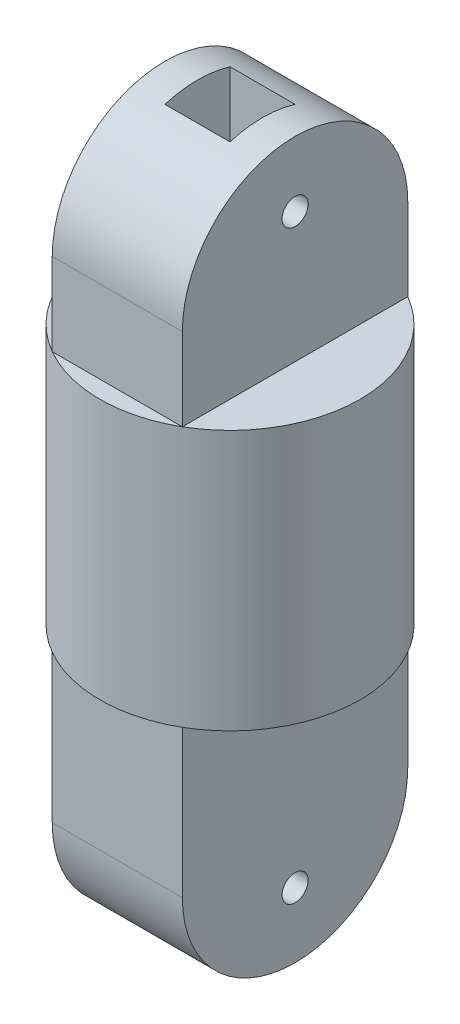
SolidWorks part; units mm, degrees
ref_plane "Front Plane" through (0, 0, 0) normal (0, 0, 1) x (1, 0, 0)
ref_plane "Top Plane" through (0, 0, 0) normal (0, 1, 0) x (1, 0, 0)
ref_plane "Right Plane" through (0, 0, 0) normal (1, 0, 0) x (0, 0, -1)
sketch "Sketch1" plane through (0, 0, 0) normal (0, 1, 0) x (1, 0, 0)
  circle A0 centre (0, 0) radius 5
  dimension "D1" = 10
extrude "Boss-Extrude1" add sketch "Sketch1" along normal blind 5 and the other way blind 5
sketch "Sketch2" plane through (0, -5, 0) normal (0, -1, 0) x (-1, 0, 0)
  line L0 (2.5, -4.3301) -> (2.5, 4.3301)
  line L1 (-2.5, -4.3301) -> (-2.5, 4.3301)
  line L2 (2.5, -4.3301) -> (-2.5, -4.3301)
  line L3 (2.5, 4.3301) -> (-2.5, 4.3301)
  circle A0 centre (0, 0) radius 5 construction
  point P4 (2.5, 0)
  dimension "D1" = 2.5
  dimension "D2" = 2.5
extrude "Boss-Extrude2" add sketch "Sketch2" along normal blind 10
sketch "Sketch3" plane through (-2.5, 0, 0) normal (-1, 0, 0) x (0, 0, 1)
  line L0 (4.3301, -15) -> (4.3301, -5) construction
  line L1 (4.3301, -15) -> (-4.3301, -15) construction
  line L2 (-4.3301, -15) -> (-4.3301, -5) construction
  line L3 (4.3301, -10.6699) -> (5.8429, -10.6699)
  line L4 (5.8429, -10.6699) -> (5.8429, -18.9142)
  line L5 (5.8429, -18.9142) -> (-6.8562, -18.9142)
  line L6 (-6.8562, -18.9142) -> (-6.8562, -10.6699)
  line L7 (-6.8562, -10.6699) -> (-4.3301, -10.6699)
  arc A0 (0, -15) -> (4.3301, -10.6699) centre (0, -10.6699) ccw
  arc A1 (0, -15) -> (-4.3301, -10.6699) centre (0, -10.6699) cw
  point P0 (0, -10.6699)
  point P5 (0, -15)
  dimension "D1" = 4.3301
  dimension "D2" = 4.3301
extrude "Cut-Extrude1" cut sketch "Sketch3" against normal blind 10
sketch "Sketch4" plane through (-2.5, 0, 0) normal (-1, 0, 0) x (0, 0, 1)
  arc A0 (-4.3301, -10.6699) -> (4.3301, -10.6699) centre (0, -10.6699) ccw construction
  point P0 (0, -12.5)
  point P4 (0, -15)
  dimension "D1" = 2.5
hole_wizard "#95 (0.03937008) Diameter Hole1" positions "Sketch5" profile "Sketch6" hole size "#95" standard "ANSI Inch" end condition through all
sketch "Sketch5" plane through (-2.5, 0, 0) normal (-1, 0, 0) x (0, 0, 1)
  point P0 (0, -12.5)
sketch "Sketch6" plane through (-2.5, -12.5, 0) normal (0, 1, 0) x (0, 0, 1)
  line L0 (0, 0) -> (0, 7.5)
  line L1 (0, 7.5) -> (0.5, 7.5)
  line L2 (0.5, 7.5) -> (0.5, 0)
  line L5 (0.5, 0) -> (0, 0)
  line L11 (0, -6.35) -> (0, 107.95) construction
  dimension "Thru Hole Dia." = 1
  dimension "Thru Hole Depth" = 7.5
sketch "Sketch7" plane through (0, 5, 0) normal (0, 1, 0) x (1, 0, 0)
  line L1 (-1.25, -1.25) -> (1.25, -1.25)
  line L2 (-1.25, -1.25) -> (-1.25, 1.25)
  line L3 (-1.25, 1.25) -> (1.25, 1.25)
  line L4 (1.25, -1.25) -> (1.25, 1.25)
  line L5 (-1.25, -1.25) -> (1.25, 1.25) construction
  line L6 (-1.25, 1.25) -> (1.25, -1.25) construction
  point P0 (0, 0)
  dimension "D1" = 2.5
  dimension "D2" = 2.5
extrude "Cut-Extrude2" cut sketch "Sketch7" against normal through all and the other way blind 10
sketch "Sketch8" plane through (0, 5, 0) normal (0, 1, 0) x (1, 0, 0)
  line L0 (-2.5, 4.3301) -> (-2.5, -4.3301)
  line L1 (0, -5.5) -> (0, 5.5) construction
  line L2 (2.5, 4.3301) -> (2.5, -4.3301)
  line L3 (-2.5, 4.3301) -> (2.5, 4.3301)
  line L4 (-2.5, -4.3301) -> (2.5, -4.3301)
  circle A0 centre (0, 0) radius 5 construction
  dimension "D1" = 2.5
extrude "Boss-Extrude3" add sketch "Sketch8" along normal blind 7.5
sketch "Sketch9" plane through (-2.5, 0, 0) normal (-1, 0, 0) x (0, 0, 1)
  line L0 (4.3301, 12.5) -> (4.3301, 5) construction
  line L2 (-4.3301, 12.5) -> (4.3301, 12.5) construction
  line L3 (0, -5.5) -> (0, 5.5) construction
  line L4 (-4.3301, 8.1699) -> (-5.3093, 8.1699)
  line L5 (-5.3093, 8.1699) -> (-5.3093, 13.1148)
  line L6 (-5.3093, 13.1148) -> (5.1388, 13.1148)
  line L7 (5.1388, 13.1148) -> (5.1388, 8.1699)
  line L8 (5.1388, 8.1699) -> (4.3301, 8.1699)
  arc A0 (-4.3301, 8.1699) -> (4.3301, 8.1699) centre (0, 8.1699) cw
  point P0 (0, 8.1699)
  point P8 (-11.2607, 9.7936)
  dimension "D1" = 0.9792
  dimension "D2" = 4.3301
  dimension "D3" = 4.9449
  dimension "D4" = 10.4481
extrude "Cut-Extrude3" cut sketch "Sketch9" against normal blind 7.5
sketch "Sketch10" plane through (-2.5, 0, 0) normal (-1, 0, 0) x (0, 0, 1)
  arc A0 (4.3301, 8.1699) -> (-4.3301, 8.1699) centre (0, 8.1699) ccw construction
  point P0 (0, 10)
  point P4 (0, 12.5)
  point P5 (0, 0)
  dimension "D1" = 2.5
hole_wizard "#95 (0.03937008) Diameter Hole2" positions "Sketch11" profile "Sketch12" hole size "#95" standard "ANSI Inch" end condition through all
sketch "Sketch11" plane through (-2.5, 0, 0) normal (-1, 0, 0) x (0, 0, 1)
  point P0 (0, 10)
sketch "Sketch12" plane through (-2.5, 10, 0) normal (0, 1, 0) x (0, 0, 1)
  line L0 (0, 0) -> (0, 7.5)
  line L1 (0, 7.5) -> (0.5, 7.5)
  line L2 (0.5, 7.5) -> (0.5, 0)
  line L5 (0.5, 0) -> (0, 0)
  line L11 (0, -6.35) -> (0, 107.95) construction
  dimension "Thru Hole Dia." = 1
  dimension "Thru Hole Depth" = 7.5
sketch "Sketch13" plane through (0, 5, 0) normal (0, -1, 0) x (1, 0, 0)
  line L1 (-1.25, -1.25) -> (1.25, -1.25)
  line L2 (-1.25, -1.25) -> (-1.25, 1.25)
  line L3 (-1.25, 1.25) -> (1.25, 1.25)
  line L4 (1.25, -1.25) -> (1.25, 1.25)
  line L5 (-1.25, -1.25) -> (1.25, 1.25) construction
  line L6 (-1.25, 1.25) -> (1.25, -1.25) construction
  point P0 (0, 0)
extrude "Cut-Extrude4" cut sketch "Sketch13" against normal blind 7.5
